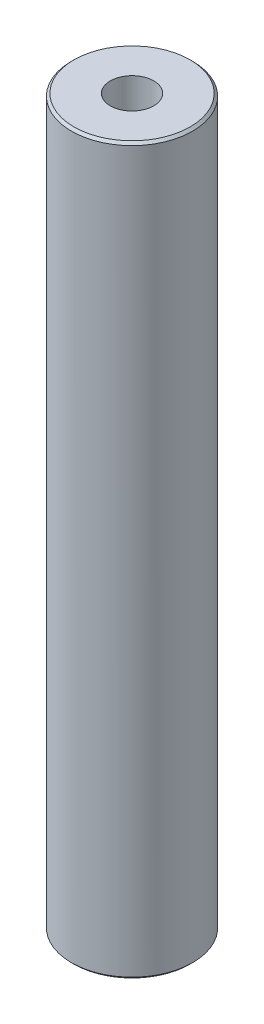
SolidWorks part; units mm, degrees
ref_plane "Front Plane" through (0, 0, 0) normal (0, 0, 1) x (1, 0, 0)
ref_plane "Top Plane" through (0, 0, 0) normal (0, 1, 0) x (1, 0, 0)
ref_plane "Right Plane" through (0, 0, 0) normal (1, 0, 0) x (0, 0, -1)
sketch "Sketch1" plane through (0, 0, 0) normal (0, 1, 0) x (1, 0, 0)
  circle A0 centre (0, 0) radius 10
  dimension "SHAFT_OD" = 20
extrude "Boss-Extrude1" add sketch "Sketch1" along normal blind 119.6977
sketch "Sketch2" plane through (0, 0, 0) normal (0, 1, 0) x (1, 0, 0)
  circle A0 centre (0, 0) radius 3.5816
  dimension "BORE_D" = 7.1631
extrude "Cut-Extrude1" cut sketch "Sketch2" along normal through all
chamfer "Chamfer1" distance 0.4075 angle 45 2 edges at (0, 119.6977, 10) (0, 0, 10)
